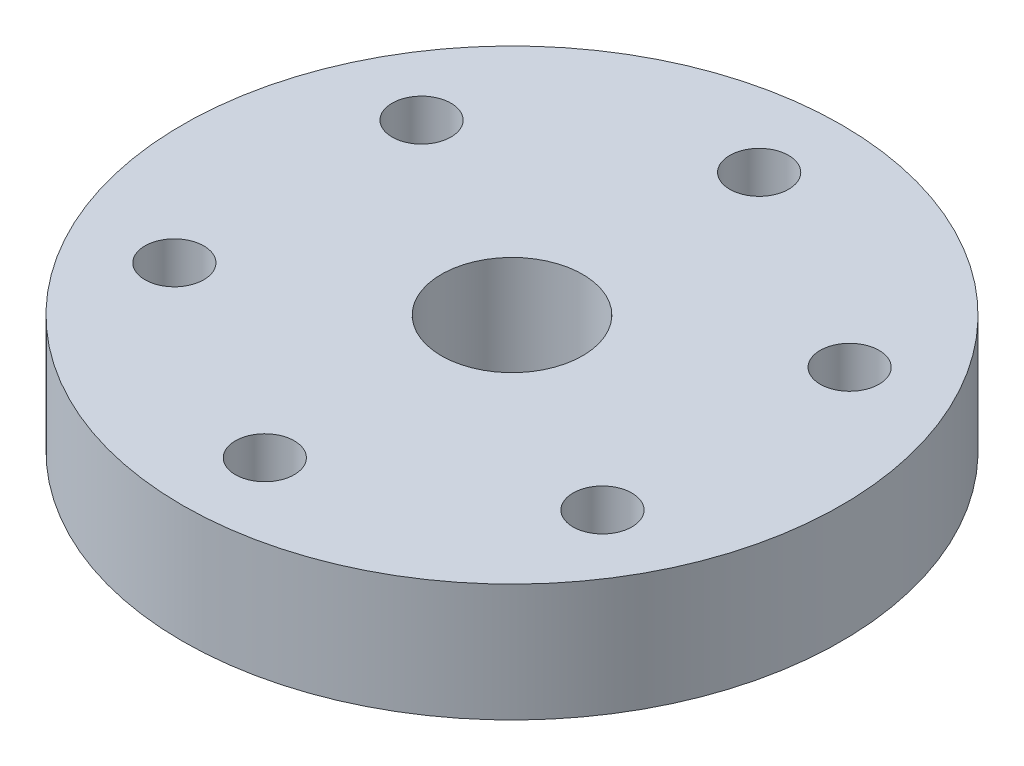
SolidWorks part; units mm, degrees
ref_plane "Front Plane" through (0, 0, 0) normal (0, 0, 1) x (1, 0, 0)
ref_plane "Top Plane" through (0, 0, 0) normal (0, 1, 0) x (1, 0, 0)
ref_plane "Right Plane" through (0, 0, 0) normal (1, 0, 0) x (0, 0, -1)
sketch "Sketch1" plane through (0, 0, 0) normal (0, 1, 0) x (1, 0, 0)
  circle A0 centre (0, 0) radius 21 construction
  circle A1 centre (0, 21) radius 2.5
  circle A2 centre (18.1865, 10.5) radius 2.5
  circle A3 centre (18.1865, -10.5) radius 2.5
  circle A4 centre (0, -21) radius 2.5
  circle A5 centre (-18.1865, -10.5) radius 2.5
  circle A6 centre (-18.1865, 10.5) radius 2.5
  circle A7 centre (0, 0) radius 28
  circle A8 centre (0, 0) radius 6
  point P18 (0, 0)
  dimension "D1" = 42
  dimension "D2" = 5
  dimension "D4" = 56
  dimension "D5" = 12
  dimension "D3" = 6
extrude "Boss-Extrude1" add sketch "Sketch1" along normal blind 10
